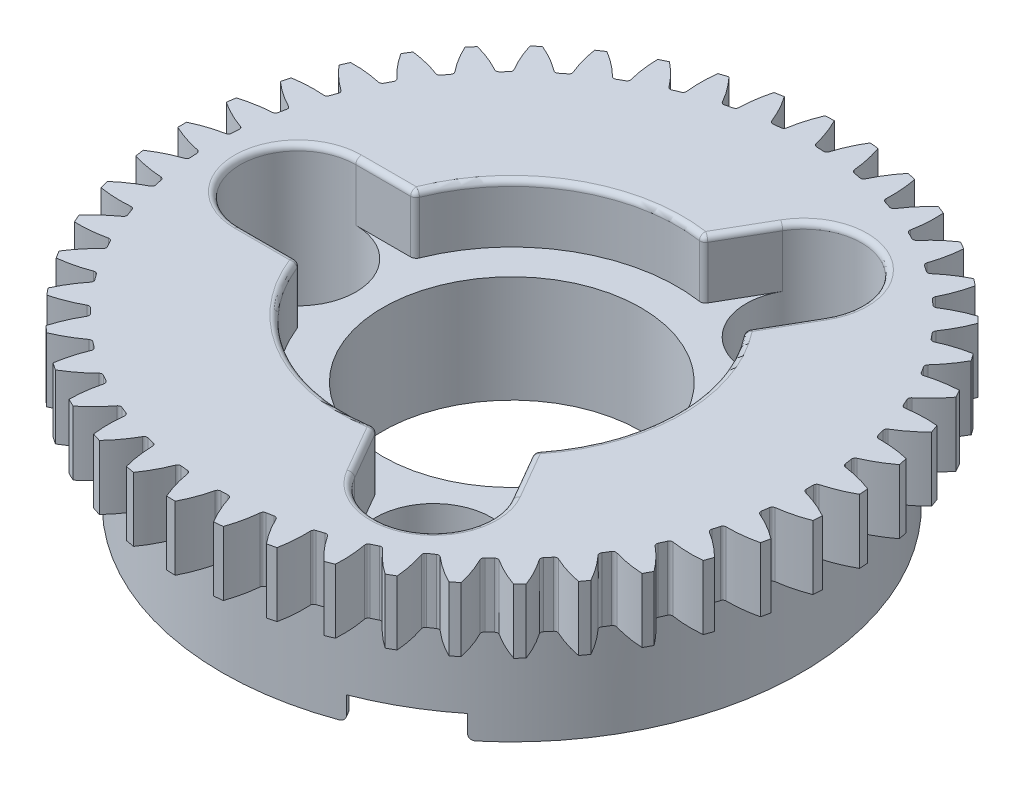
SolidWorks part; units mm, degrees
ref_plane "Front Plane" through (0, 0, 0) normal (0, 0, 1) x (1, 0, 0)
ref_plane "Top Plane" through (0, 0, 0) normal (0, 1, 0) x (1, 0, 0)
ref_plane "Right Plane" through (0, 0, 0) normal (1, 0, 0) x (0, 0, -1)
sketch "Sketch2" plane through (0, 0, 0) normal (0, 1, 0) x (1, 0, 0)
  circle A0 centre (0, 0) radius 26.56
  circle A1 centre (-19.0525, 0) radius 5.15
  circle A2 centre (9.5262, 16.4999) radius 5.15
  circle A3 centre (9.5262, -16.4999) radius 5.15
  circle A5 centre (0, 0) radius 11.5
  point P2 (0, 0)
  point P11 (0, 0)
  point P12 (13.6656, 4.178)
  dimension "D2" = 3
  dimension "D1" = 23
  dimension "D4" = 53.12
  dimension "D5" = 10.3
  dimension "D3" = 19.0525
extrude "Boss-Extrude2" add sketch "Sketch2" along normal blind 5.72
sketch "Sketch4" plane through (0, 0, 0) normal (0, -1, 0) x (1, 0, 0)
  circle A0 centre (9.5262, 16.4999) radius 5.15 construction
  circle A1 centre (9.5262, 16.4999) radius 5.15
  circle A2 centre (0, 0) radius 9.625
  circle A19 centre (0, 0) radius 25.815
  point P6 (-1.3086, -0.0126)
  point P13 (12.187, -21.1085)
  point P15 (-24.374, 0)
  point P17 (12.187, 21.1085)
  point P18 (-12.5475, 0)
  point P25 (16.9495, -21.1085)
  point P26 (16.9495, 21.1085)
  point P27 (-26.7552, 4.1244)
  point P28 (9.8057, 25.2329)
  point P29 (9.8057, -25.2329)
  point P30 (-26.7552, -4.1244)
  point P31 (16.4175, -16.723)
  point P36 (16.4175, 16.723)
  point P46 (13.9118, 4.2533)
  circle M1 centre (9.5262, -16.4999) radius 5.15
  circle M2 centre (-19.0525, 0) radius 5.15
  circle M4 centre (0, 0) radius 11.5
  circle M5 centre (9.5262, 16.4999) radius 5.15
  dimension "D1" = 19.25
extrude "Boss-Extrude3" add sketch "Sketch4" along normal blind 8.98 contours A19 M1 M5 M4 M2 region at (-25.0848, 0, 0)
sketch "Sketch7" plane through (0, 5.72, 0) normal (0, 1, 0) x (1, 0, 0)
  line L0 (0, 0) -> (9.5262, 16.4999) construction
  line L1 (11.3709, -9.395) -> (13.9863, -13.9249)
  line L2 (11.3709, 9.395) -> (13.9863, 13.9249)
  line L4 (2.4508, -14.545) -> (5.0662, -19.0749)
  line L5 (-13.8217, -5.15) -> (-19.0525, -5.15)
  line L6 (-13.8217, 5.15) -> (-19.0525, 5.15)
  line L7 (2.4508, 14.545) -> (5.0662, 19.0749)
  arc A0 (2.4508, 14.545) -> (-13.8217, 5.15) centre (0, 0) ccw
  arc A1 (13.9863, -13.9249) -> (5.0662, -19.0749) centre (9.5262, -16.4999) ccw
  arc A2 (-19.0525, -5.15) -> (-19.0525, 5.15) centre (-19.0525, 0) ccw
  circle A4 centre (9.5262, 16.4999) radius 5.15 construction
  arc A5 (5.0662, 19.0749) -> (13.9863, 13.9249) centre (9.5262, 16.4999) ccw
  arc A6 (-13.8217, -5.15) -> (2.4508, -14.545) centre (0, 0) ccw
  arc A8 (11.3709, -9.395) -> (11.3709, 9.395) centre (0, 0) ccw
  point P21 (0, 0)
  point P28 (0, 0)
  point P29 (0, 0)
  dimension "D1" = 29.5
  dimension "D2" = 3
extrude "Cut-Extrude7" cut sketch "Sketch7" against normal blind 5.178
sketch "Sketch10" plane through (0, 5.72, 0) normal (0, 1, 0) x (1, 0, 0)
  circle A3 centre (0, 0) radius 25.56
  circle A4 centre (0, 0) radius 25.56
  dimension "D1" = 1
sketch "Sketch12" plane through (0, 5.72, 0) normal (0, 1, 0) x (1, 0, 0)
  line L0 (0, 0) -> (15.065, -26.0933) construction
  line L1 (13.28, -23.0016) -> (14.4058, -22.3516) construction
  arc A0 (11.9245, -23.7327) -> (14.5908, -22.1933) centre (0, 0) ccw
  circle A1 centre (0, 0) radius 26.56 construction
  circle A2 centre (0, 0) radius 29.38
  arc A3 (14.5908, -22.1933) -> (14.4715, -22.5401) centre (14.7557, -22.4439) ccw
  circle A4 centre (0, 0) radius 26.56 construction
  arc A5 (15.029, -25.2451) -> (14.4715, -22.5401) centre (3.8151, -26.1463) ccw
  arc A6 (14.3484, -25.638) -> (12.2846, -23.8027) centre (20.7358, -16.3771) cw
  arc A7 (11.9245, -23.7327) -> (12.2846, -23.8027) centre (12.0592, -24.0007) cw
  point P18 (25.3995, 7.7654)
  circle M13 centre (0, 0) radius 26.56
  dimension "D1" = 0.3
  dimension "D2" = 58.76
  dimension "D3" = 30.13
  dimension "D4" = 1.3
  dimension "D5" = 11.25
extrude "Boss-Extrude4" add sketch "Sketch12" against normal up to surface (5.72 mm away) contours A7 A6 A2 A5 A3 M13 region at (13.8631, 5.72, 24.0116) up to face at (0, 0, 26.56)
pattern_circular "CirPattern2" count 45 over 360 about axis through (0, 5.72, 0) along (0, 1, 0) of "Boss-Extrude4"
sketch "Sketch9" plane through (0, -8.98, 0) normal (0, -1, 0) x (1, 0, 0)
  line L0 (9.5262, -16.4999) -> (0, 0) construction
  line L1 (9.0232, -23.532) -> (9.3331, -24.0688)
  line L2 (15.8677, -19.5803) -> (16.1776, -20.1171)
  line L3 (-24.8909, 3.9517) -> (-25.5108, 3.9517)
  line L4 (-24.8909, -3.9517) -> (-25.5108, -3.9517)
  line L5 (15.8677, 19.5803) -> (16.1776, 20.1171)
  line L6 (9.0232, 23.532) -> (9.3331, 24.0688)
  arc A2 (-24.8909, -3.9517) -> (-24.8909, 3.9517) centre (-19.0525, 0) ccw
  arc A3 (16.5762, -16.4999) -> (16.5762, -16.4999) centre (9.5262, -16.4999) ccw
  arc A4 (15.8677, -19.5803) -> (9.0232, -23.532) centre (9.5262, -16.4999) ccw
  arc A5 (-25.5108, 3.9517) -> (-25.5108, -3.9517) centre (0, 0) ccw
  circle A6 centre (0, 0) radius 25.815 construction
  arc A7 (9.3331, -24.0688) -> (16.1776, -20.1171) centre (0, 0) ccw
  arc A8 (9.0232, 23.532) -> (15.8677, 19.5803) centre (9.5263, 16.4999) ccw
  arc A9 (16.1776, 20.1171) -> (9.3331, 24.0688) centre (0, 0) ccw
  point P9 (0, 0)
  point P22 (0, 0)
  dimension "D1" = 1.9
  dimension "D2" = 3
extrude "Cut-Extrude8" cut sketch "Sketch9" against normal blind 2.0875
fillet "Fillet1" radius 0.5 18 edges at (3.7585, 5.72, 16.81) (12.1012, 5.72, 20.96) (3.7585, 5.72, -16.81) (12.1012, 5.72, -20.96) (-16.4371, 5.72, 5.15) (-24.2025, 5.72, 0) (-13.8217, 3.131, 5.15) (-7.375, 5.72, 12.7739) (2.4508, 3.131, 14.545) (12.6786, 5.72, 11.66) (11.3709, 3.131, 9.395) (11.3709, 3.131, -9.395) (14.75, 5.72, 0) (12.6786, 5.72, -11.66) (2.4508, 3.131, -14.545) (-13.8217, 3.131, -5.15) (-16.4371, 5.72, -5.15) (-7.375, 5.72, -12.7739)
fillet "Fillet2" radius 0.5 9 edges at (16.0226, -8.98, 19.8487) (9.1782, -8.98, 23.8004) (6.0013, -8.98, 10.3945) (-25.2008, -8.98, 3.9517) (-25.2008, -8.98, -3.9517) (-12.0025, -8.98, 0) (16.0226, -8.98, -19.8487) (9.1782, -8.98, -23.8004) (6.0012, -8.98, -10.3945)
